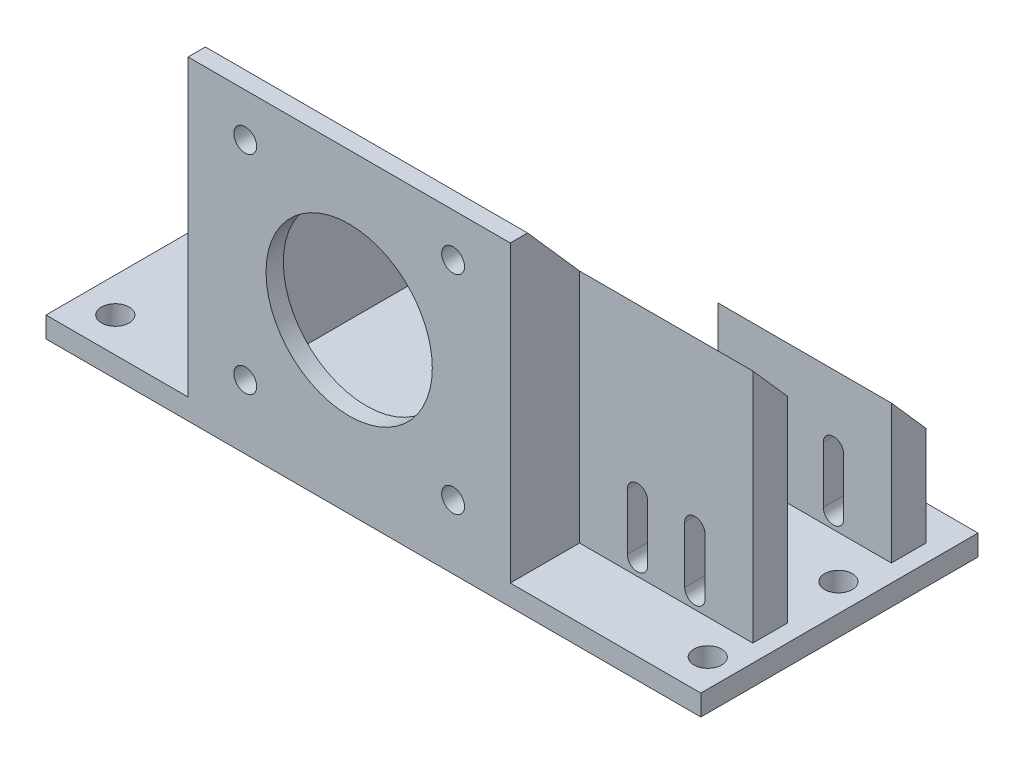
SolidWorks part; units mm, degrees
ref_plane "Front Plane" through (0, 0, 0) normal (0, 0, 1) x (1, 0, 0)
ref_plane "Top Plane" through (0, 0, 0) normal (0, 1, 0) x (1, 0, 0)
ref_plane "Right Plane" through (0, 0, 0) normal (1, 0, 0) x (0, 0, -1)
sketch "Sketch1" plane through (0, 0, 0) normal (0, 1, 0) x (1, 0, 0)
  line L0 (41, 40) -> (41, 0) construction
  line L1 (0, 0) -> (82, 0)
  line L2 (0, 0) -> (0, 40)
  line L3 (0, 40) -> (82, 40)
  line L4 (82, 0) -> (82, 40)
  line L5 (41, 20) -> (18, 20) construction
  line L6 (82, 14.3756) -> (74, 14.3756) construction
  line L7 (18, 40) -> (18, 0) construction
  line L8 (74, 40) -> (74, 0) construction
  line L10 (0, 40) -> (-12.5, 40)
  line L11 (0, 40) -> (0, 0)
  line L12 (0, 0) -> (-12.5, 0)
  line L13 (-12.5, 40) -> (-12.5, 0)
  circle A0 centre (-7.5, 23.86) radius 2
  circle A1 centre (4, 23.86) radius 2 construction
  circle A2 centre (4, 5) radius 2 construction
  circle A3 centre (-7.5, 5) radius 2
  circle A4 centre (78, 23.86) radius 2
  circle A5 centre (78, 5) radius 2
  dimension "D3" = 4
  dimension "D7" = 18.86
  dimension "D14" = 4
  dimension "D1" = 82
  dimension "D2" = 40
  dimension "D4" = 4
  dimension "D5" = 4
  dimension "D6" = 12.5
  dimension "D8" = 18.86
  dimension "D9" = 5
  dimension "D10" = 23
  dimension "D11" = 8
  dimension "D12" = 5
  dimension "D13" = 5
extrude "Boss-Extrude1" add sketch "Sketch1" along normal blind 3 contours L1 L4 L3 L2 A4 A5 | L10 L13 L12 L2 A3 A0 region at (40.7143, 0, -20.043) region at (-6.1838, 0, -20.2948)
sketch "Sketch2" plane through (0, 3, 0) normal (0, 1, 0) x (1, 0, 0)
  line L0 (10, 40) -> (10, 0)
  line L4 (8, 40) -> (8, 0)
  line L5 (54.5, 40) -> (54.5, 0)
  line L6 (52.5, 40) -> (52.5, 0)
  line L7 (10, 2.5) -> (52.5, 2.5)
  line L9 (-12.5, 0) -> (82, 0)
  line L10 (82, 0) -> (82, 40)
  line L11 (82, 40) -> (-12.5, 40)
  line L12 (-12.5, 40) -> (-12.5, 0)
  line L13 (-12.5, 0) -> (82, 0)
  line L14 (82, 0) -> (82, 40)
  line L15 (82, 40) -> (-12.5, 40)
  line L16 (-12.5, 40) -> (-12.5, 0)
  dimension "D2" = 42.5
  dimension "D3" = 2
  dimension "D4" = 2
  dimension "D5" = 2.5
  dimension "D6" = 27.5
  dimension "D1" = 0
extrude "Boss-Extrude2" add sketch "Sketch2" along normal blind 42.5 contours L0 L15 L4 L13 | L0 L13 L6 L7 | L5 L15 L6 L13 region at (9, 3, -20) region at (31.25, 3, -1.25) region at (53.5, 3, -20)
sketch "Sketch3" plane through (54.5, 6, 0) normal (-1, 0, 0) x (0, 0, -1)
  line L1 (40, -39.5) -> (0, -39.5)
  line L2 (2.5, -39.5) -> (40, 3)
  line L5 (0, 3) -> (40, 3)
  line L7 (40, 3) -> (0, 3)
  line L8 (40, -39.5) -> (40, 3)
  line L9 (0, -39.5) -> (40, -39.5)
  line L10 (0, 3) -> (0, -39.5)
  line L11 (40, 3) -> (0, 3)
  line L12 (40, -39.5) -> (40, 3)
  line L13 (0, -39.5) -> (40, -39.5)
  line L14 (0, 3) -> (0, -39.5)
  line M30 (40, 3) -> (40, -39.5)
  line M31 (40, -39.5) -> (0, -39.5)
  dimension "D2" = 40
  dimension "D1" = 56.6789
  dimension "D3" = 0
extrude "Cut-Extrude1" cut sketch "Sketch3" along normal through all contours L2 M31 M30 region at (54.5, 31.3333, -27.5)
sketch "Sketch4" plane through (0, 0, 0) normal (0, 0, 1) x (1, 0, 0)
  line L0 (10, 45.5) -> (52.5, 3) construction
  line L1 (52.5, 45.5) -> (10, 3) construction
  line L6 (10, 3) -> (52.5, 3)
  line L7 (10, 45.5) -> (10, 3)
  line L8 (52.5, 45.5) -> (10, 45.5)
  line L9 (52.5, 3) -> (52.5, 45.5)
  line L10 (10, 3) -> (52.5, 3)
  line L11 (10, 45.5) -> (10, 3)
  line L12 (52.5, 45.5) -> (10, 45.5)
  line L13 (52.5, 3) -> (52.5, 45.5)
  circle A0 centre (31.25, 24.25) radius 12
  circle A1 centre (16.25, 39.25) radius 1.65
  circle A2 centre (16.25, 9.25) radius 1.65
  circle A3 centre (46.25, 9.25) radius 1.65
  circle A4 centre (46.25, 39.25) radius 1.65
  dimension "D2" = 24
  dimension "D3" = 3.3
  dimension "D4" = 30
  dimension "D1" = 0
extrude "Cut-Extrude2" cut sketch "Sketch4" against normal through all contours A0 | A2 | A1 | A4 | A3 region at (31.25, 24.25, 0)
sketch "Sketch7" plane through (0, 3, 0) normal (0, 1, 0) x (1, 0, 0)
  line L0 (54.5, 10) -> (79.5, 10)
  line L2 (79.5, 10) -> (79.5, 15)
  line L3 (79.5, 15) -> (54.5, 15)
  line L4 (54.5, 15) -> (54.5, 30)
  line L5 (54.5, 30) -> (79.5, 30)
  line L6 (79.5, 30) -> (79.5, 35)
  line L7 (79.5, 35) -> (54.5, 35)
  line L8 (54.5, 40) -> (54.5, 35)
  line L13 (82, 40) -> (54.5, 40)
  line L14 (54.5, 40) -> (54.5, 0)
  line L15 (54.5, 0) -> (82, 0)
  line L16 (82, 40) -> (54.5, 40)
  line L17 (54.5, 10) -> (54.5, 0)
  line L18 (54.5, 0) -> (82, 0)
  line L19 (82, 0) -> (82, 40)
  line L20 (82, 0) -> (82, 40)
  line L21 (82, 40) -> (54.5, 40)
  line L22 (54.5, 40) -> (54.5, 0)
  line L23 (54.5, 0) -> (82, 0)
  line L24 (82, 0) -> (82, 40)
  line M37 (54.5, 40) -> (54.5, 0)
  dimension "D2" = 5
  dimension "D3" = 5
  dimension "D4" = 15
  dimension "D1" = 0
extrude "Boss-Extrude3" add sketch "Sketch7" along normal blind 20 contours L6 L7 L5 region at (67, 3, -32.5)
extrude "Boss-Extrude4" add sketch "Sketch7<3>" along normal up to surface (34 mm away) contours L2 L3 L0 M37 region at (67, 3, -12.5) up to face at (53.8333, 20, -25)
sketch "Sketch7<3>" plane through (0, 3, 0) normal (0, 1, 0) x (1, 0, 0) same geometry as "Sketch7"
sketch "Sketch9" plane through (0, 0, -10) normal (0, 0, 1) x (1, 0, 0)
  line L0 (62.8561, 13.1701) -> (62.8561, 5.0521) construction
  line L1 (64.3301, 13.1701) -> (64.3301, 5.0521)
  line L2 (61.3822, 13.1701) -> (61.3822, 5.0521)
  line L3 (67, 37) -> (67, 3) construction
  line L8 (54.5, 3) -> (79.5, 3) construction
  line L9 (71.1439, 13.1701) -> (71.1439, 5.0521) construction
  line L10 (69.6699, 13.1701) -> (69.6699, 5.0521)
  line L11 (72.6178, 13.1701) -> (72.6178, 5.0521)
  arc A0 (64.3301, 13.1701) -> (61.3822, 13.1701) centre (62.8561, 13.1701) ccw
  arc A1 (61.3822, 5.0521) -> (64.3301, 5.0521) centre (62.8561, 5.0521) ccw
  arc A2 (69.6699, 13.1701) -> (72.6178, 13.1701) centre (71.1439, 13.1701) cw
  arc A3 (72.6178, 5.0521) -> (69.6699, 5.0521) centre (71.1439, 5.0521) cw
  point P2 (62.8561, 9.1111)
  point P14 (71.1439, 9.1111)
  point P15 (67, 37)
extrude "Cut-Extrude3" cut sketch "Sketch9" against normal through all contours L2 A1 L1 A0 | A3 L11 A2 L10 region at (62.8561, 9.1111, -10) region at (71.1439, 9.1111, -10)
sketch "Sketch11" plane through (54.5, 0, 0) normal (-1, 0, 0) x (0, 0, 1)
  line L0 (-30, 23) -> (-35, 17.3326)
  line L1 (-35, 23) -> (-35, 8.6667) construction
  line L6 (-35, 23) -> (-35, 8.6667)
  line L7 (-35, 8.6667) -> (-30, 14.3333)
  line L8 (-30, 14.3333) -> (-30, 23)
  line L9 (-30, 23) -> (-35, 23)
  line L10 (-35, 23) -> (-35, 8.6667)
  line L11 (-35, 8.6667) -> (-30, 14.3333)
  line L12 (-30, 14.3333) -> (-30, 23)
  line L13 (-30, 23) -> (-35, 23)
  line M2 (-35, 23) -> (-35, 8.6667)
  line M5 (-30, 23) -> (-35, 23)
  dimension "D2" = 41.424
  dimension "D3" = 41.42
  dimension "D1" = 0
extrude "Cut-Extrude4" cut sketch "Sketch11" against normal through all contours L0 M5 M2 region at (54.5, 21.1109, -33.3333)
